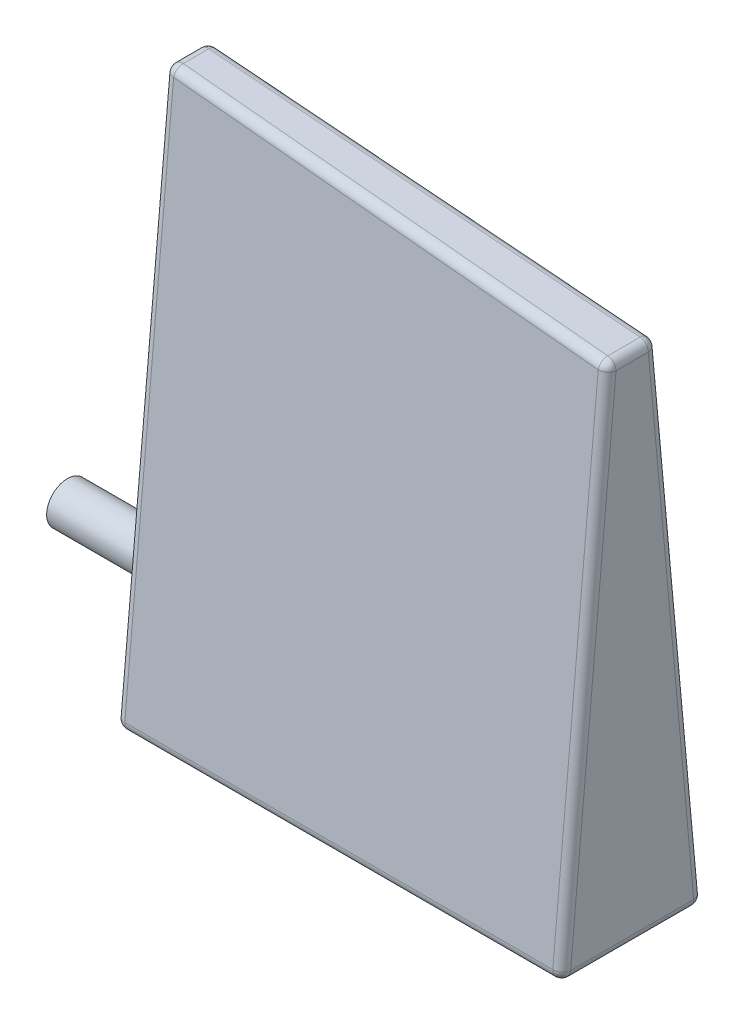
SolidWorks part; units mm, degrees
ref_plane "Alzado" through (0, 0, 0) normal (0, 0, 1) x (1, 0, 0)
ref_plane "Planta" through (0, 0, 0) normal (0, 1, 0) x (1, 0, 0)
ref_plane "Vista lateral" through (0, 0, 0) normal (1, 0, 0) x (0, 0, -1)
sketch "Croquis1" plane through (0, 0, 0) normal (1, 0, 0) x (0, 0, -1)
  line L0 (-6, -8.5648) -> (6, -8.5648)
  line L1 (0, 0) -> (0, -8.5648) construction
  line L2 (-1.75, 37.9352) -> (1.75, 37.9352)
  line L3 (0, 0) -> (0, 37.9352) construction
  line L4 (-6, -8.5648) -> (-1.75, 37.9352)
  line L5 (6, -8.5648) -> (1.75, 37.9352)
  point P3 (0, -8.5648)
  dimension "D1" = 12
  dimension "D2" = 46.5
  dimension "D3" = 3.5
extrude "Saliente-Extruir1" add sketch "Croquis1" along normal blind 37.5
sketch "Croquis2" plane through (0, 0, 0) normal (0, 0, 1) x (1, 0, 0)
  line L0 (0, 37.9352) -> (37.5, 37.9352)
  line L1 (37.5, 37.9352) -> (37.5, 34.6544)
  line L2 (37.5, 37.9352) -> (37.5, -8.5648) construction
  line L3 (37.5, 34.6544) -> (0, 37.9352)
  dimension "D1" = 95
extrude "Cortar-Extruir1" cut sketch "Croquis2" against normal blind 37.5 and the other way blind 37.5
sketch "Croquis3" plane through (0, 0, 0) normal (-1, 0, 0) x (0, 0, 1)
  line L0 (0, -8.5648) -> (0, -0.0648) construction
  line L1 (6, -8.5648) -> (-6, -8.5648) construction
  circle A0 centre (0, -0.0648) radius 1.75
  dimension "D2" = 3.5
  dimension "D1" = 8.5
extrude "Saliente-Extruir2" add sketch "Croquis3" along normal blind 10
fillet "Redondeo1" radius 0.75 12 edges at (0, -8.5648, 0) (18.75, -8.5648, -6) (18.75, -8.5648, 6) (37.5, -8.5648, 0) (37.5, 13.0448, 4.0249) (37.5, 13.0448, -4.0249) (37.5, 34.6544, 0) (0, 37.9352, 0) (0, 14.6852, 3.875) (0, 14.6852, -3.875) (18.75, 36.2948, 1.8999) (18.75, 36.2948, -1.8999)
